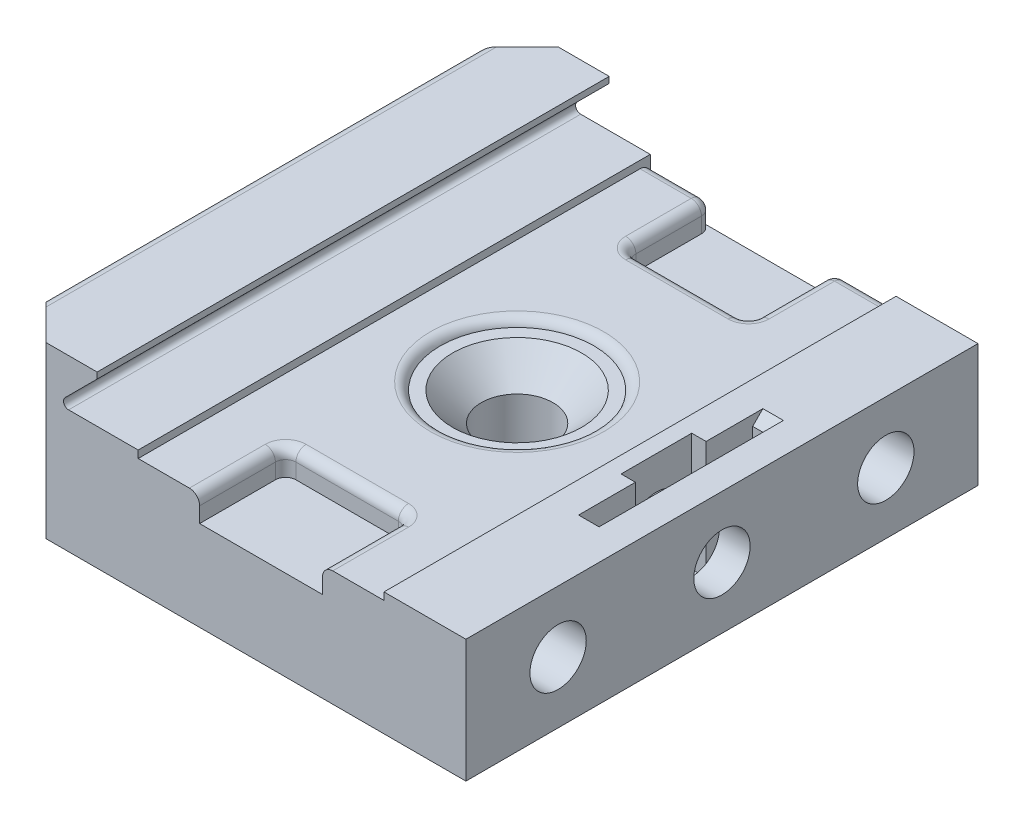
SolidWorks part; units mm, degrees
ref_plane "Front Plane" through (0, 0, 0) normal (0, 0, 1) x (1, 0, 0)
ref_plane "Top Plane" through (0, 0, 0) normal (0, 1, 0) x (1, 0, 0)
ref_plane "Right Plane" through (0, 0, 0) normal (1, 0, 0) x (0, 0, -1)
sketch "Sketch1" plane through (0, 0, 0) normal (0, 1, 0) x (1, 0, 0)
  line L1 (22.5, -25) -> (-22.5, -25)
  line L2 (22.5, -25) -> (22.5, 25)
  line L3 (22.5, 25) -> (-22.5, 25)
  line L4 (-22.5, -25) -> (-22.5, 25)
  line L5 (22.5, -25) -> (-22.5, 25) construction
  line L6 (22.5, 25) -> (-22.5, -25) construction
  point P0 (0, 0)
  dimension "D1" = 45
  dimension "D2" = 50
extrude "Boss-Extrude1" add sketch "Sketch1" along normal blind 16
sketch "Sketch3" plane through (0, 0, 25) normal (0, 0, 1) x (1, 0, 0)
  line L0 (-13.5, 16) -> (-17.5, 12)
  line L1 (22.5, 16) -> (-13.5, 16)
  line L2 (22.5, 16) -> (22.5, 12)
  line L3 (22.5, 12) -> (-17.5, 12)
  dimension "D1" = 40
  dimension "D2" = 36
  dimension "D3" = 45
extrude "Cut-Extrude1" cut sketch "Sketch3" against normal through all
sketch "Sketch4" plane through (0, 12, 0) normal (0, 1, 0) x (1, 0, 0)
  line L0 (22.5, 25) -> (-17.5, -25) construction
  line L1 (-17.5, -25) -> (22.5, -25)
  line L2 (-17.5, -25) -> (-17.5, 25)
  line L3 (-17.5, 25) -> (22.5, 25)
  line L4 (22.5, -25) -> (22.5, 25)
  line L5 (22.5, -25) -> (-17.5, 25) construction
  line L7 (-9.5, -25) -> (14.5, -25)
  line L8 (-9.5, -25) -> (-9.5, 25)
  line L9 (-9.5, 25) -> (14.5, 25)
  line L10 (14.5, -25) -> (14.5, 25)
  line L11 (-9.5, -25) -> (14.5, 25) construction
  line L12 (-9.5, 25) -> (14.5, -25) construction
  point P6 (2.5, 0)
  dimension "D1" = 24
extrude "Cut-Extrude2" cut sketch "Sketch4" against normal blind 0.72 contours L8 L9 L10 L7
sketch "Sketch5" plane through (0, 0, 25) normal (0, 0, 1) x (1, 0, 0)
  line L0 (-22.5, 16) -> (-13.5, 16)
  line L1 (-13.5, 16) -> (-13.51, 15.99)
  line L2 (-13.5, 16) -> (-17.5, 12) construction
  line L3 (-13.51, 15.99) -> (-22.5, 15.99)
  line L4 (-22.5, 16) -> (-22.5, 0) construction
  line L5 (-22.5, 15.99) -> (-22.5, 16)
  dimension "D1" = 0.01
extrude "Cut-Extrude3" cut sketch "Sketch5" against normal through all
sketch "Sketch8" plane through (0, 11.28, 0) normal (0, 1, 0) x (1, 0, 0)
  line L0 (-9.5, -25) -> (-9.5, 25) construction
  line L1 (-9.5, -25) -> (14.5, -25) construction
  circle A0 centre (2.5, 0) radius 7.5
  dimension "D1" = 12
  dimension "D2" = 25
extrude "Cut-Extrude4" cut sketch "Sketch8" against normal blind 0.72
hole_wizard "CSK for M6 Flat Head Machine Screw1" positions "Sketch9" profile "Sketch10" countersink size "M6" standard "ANSI Metric" end condition through all
sketch "Sketch9" plane through (0, 10.56, 0) normal (0, 1, 0) x (1, 0, 0)
  point P0 (2.5, 0)
sketch "Sketch10" plane through (2.5, 10.56, 0) normal (1, 0, 0) x (0, 0, 1)
  line L0 (0, 0) -> (0, 10.56)
  line L1 (0, 10.56) -> (3.5, 10.56)
  line L2 (3.5, 10.56) -> (3.5, 2.8)
  line L3 (3.5, 2.8) -> (6.3, 0)
  line L5 (6.3, 0) -> (0, 0)
  line L6 (-3.5, 2.8) -> (-6.3, 0) construction
  line L11 (0, -6.35) -> (0, 107.95) construction
  dimension "Thru Hole Dia." = 7
  dimension "Thru Hole Depth" = 10.56
  dimension "Near C'Sink Dia." = 12.6
  dimension "Near C'Sink Angle" = 90
sketch "Sketch12" plane through (0, 11.28, 0) normal (0, 1, 0) x (1, 0, 0)
  line L0 (-9.5, 25) -> (14.5, 25) construction
  line L1 (7.5, 16.6) -> (-2.5, 16.6)
  line L2 (8.5, 17.6) -> (8.5, 25)
  line L4 (-3.5, 17.6) -> (-3.5, 25)
  line L5 (-3.5, 21.3) -> (8.5, 21.3) construction
  line L6 (2.5, 25) -> (2.5, 16.6) construction
  line L7 (-3.5, 25) -> (8.5, 25)
  line L8 (-9.5, -25) -> (-9.5, 25) construction
  arc A0 (7.5, 16.6) -> (8.5, 17.6) centre (7.5, 17.6) ccw
  arc A1 (-2.5, 16.6) -> (-3.5, 17.6) centre (-2.5, 17.6) cw
  point P0 (2.5, 25)
  point P9 (8.5, 16.6)
  point P12 (-3.5, 16.6)
  point P17 (2.5, 21.3)
  dimension "D2" = 1
  dimension "D1" = 12
  dimension "D3" = 12
  dimension "D4" = 0
  dimension "D5" = 7.4
extrude "Cut-Extrude5" cut sketch "Sketch12" against normal blind 2.5
fillet "Fillet1" radius 1 2 edges at (8.5, 10.03, -25) (-3.5, 10.03, -25)
mirror "Mirror2" about plane through (0, 0, 0) normal (0, 0, 1) of "Cut-Extrude5"
fillet "Fillet2" radius 1 15 edges at (-7, 11.28, -25) (-3.7929, 11.28, -24.7071) (12, 11.28, -25) (8.7929, 11.28, -24.7071) (8.5, 11.28, -20.8) (8.2071, 11.28, -16.8929) (2.5, 11.28, -16.6) (-3.2071, 11.28, -16.8929) (-3.5, 11.28, 21.3) (-3.2071, 11.28, 16.8929) (8.5, 11.28, 21.3) (8.2071, 11.28, 16.8929) (-5, 11.28, 0) (-3.5, 11.28, -20.8) (2.5, 11.28, 16.6)
fillet "Fillet4" radius 0.5 1 edges at (-17.5, 12, 0)
sketch "Sketch14" plane through (0, 12, 0) normal (0, 1, 0) x (1, 0, 0)
  line L0 (14.5, 25) -> (22.5, 25) construction
  line L1 (19.5, -8) -> (17.5, -8)
  line L2 (19.5, -8) -> (19.5, 8)
  line L3 (19.5, 8) -> (17.5, 8)
  line L4 (17.5, -8) -> (17.5, -3.45)
  line L5 (19.5, -8) -> (17.5, 8) construction
  line L6 (19.5, 8) -> (17.5, -8) construction
  line L7 (17.5, 3.45) -> (16.1, 3.45)
  line L8 (17.5, -3.45) -> (16.1, -3.45)
  line L11 (16.1, -3.45) -> (16.1, 3.45)
  line L12 (19.5, -1.4375) -> (16.1, 3.45) construction
  line L13 (19.5, 1.4375) -> (16.1, -3.45) construction
  line L14 (17.5, 3.45) -> (17.5, 8)
  point P0 (18.5, 0)
  point P7 (18.5, 0)
  dimension "D1" = 16
  dimension "D2" = 25
  dimension "D3" = 2
  dimension "D4" = 6.9
  dimension "D5" = 1.4
  dimension "D6" = 4.55
extrude "Cut-Extrude7" cut sketch "Sketch14" against normal blind 11.5
sketch "Sketch18" plane through (22.5, 0, 0) normal (1, 0, 0) x (0, 0, -1)
  circle A0 centre (0, 6) radius 2.75
  dimension "D1" = 5.5
extrude "Cut-Extrude8" cut sketch "Sketch18" against normal blind 14.5
sketch "Sketch19" plane through (22.5, 0, 0) normal (1, 0, 0) x (0, 0, -1)
  line L0 (-25, 12) -> (-25, 0) construction
  line L1 (25, 12) -> (25, 0) construction
  circle A0 centre (-16, 6) radius 2.75
  circle A1 centre (16, 6) radius 2.75
  dimension "D3" = 5.5
  dimension "D4" = 5.5
  dimension "D1" = 9
  dimension "D2" = 9
extrude "Cut-Extrude9" cut sketch "Sketch19" against normal blind 10
sketch "Sketch20" plane through (0, 0, 0) normal (0, -1, 0) x (-1, 0, 0)
  line L1 (-4.65, 8.25) -> (-0.35, 8.25)
  line L2 (-4.65, 8.25) -> (-4.65, -8.25)
  line L3 (-4.65, -8.25) -> (-0.35, -8.25)
  line L4 (-0.35, 8.25) -> (-0.35, -8.25)
  line L5 (-4.65, 8.25) -> (-0.35, -8.25) construction
  line L6 (-4.65, -8.25) -> (-0.35, 8.25) construction
  dimension "D1" = 4.3
  dimension "D2" = 16.5
extrude "Cut-Extrude10" [suppressed] cut sketch "Sketch20" against normal blind 2
sketch "Sketch21" plane through (0, 15.99, 0) normal (0, 1, 0) x (1, 0, 0)
  line L1 (-22.5, 25) -> (-13.51, 25)
  line L2 (-22.5, 25) -> (-22.5, -25)
  line L3 (-22.5, -25) -> (-13.51, -25)
  line L4 (-13.51, 25) -> (-13.51, -25)
extrude "Boss-Extrude2" add sketch "Sketch21" along normal blind 0.6
chamfer "Chamfer1" distance 4 angle 45 2 edges at (-22.5, 8.295, -25) (-22.5, 8.295, 25)
fillet "Fillet5" radius 1 1 edges at (-22.5, 16.59, 0)
sketch "Sketch23" plane through (0, 10.56, 0) normal (0, 1, 0) x (1, 0, 0)
  line L1 (2.5, 6.6188) -> (-3.2321, 3.3094)
  line L2 (-3.2321, 3.3094) -> (-3.2321, -3.3094)
  line L3 (-3.2321, -3.3094) -> (2.5, -6.6188)
  line L4 (2.5, -6.6188) -> (8.2321, -3.3094)
  line L5 (8.2321, -3.3094) -> (8.2321, 3.3094)
  line L6 (8.2321, 3.3094) -> (2.5, 6.6188)
  circle A0 centre (2.5, 0) radius 5.7321 construction
extrude "Cut-Extrude11" [suppressed] cut sketch "Sketch23" against normal blind 4
chamfer "Chamfer2" distance 1 angle 45 2 edges at (18.5, 12, 8) (18.5, 12, -8)
